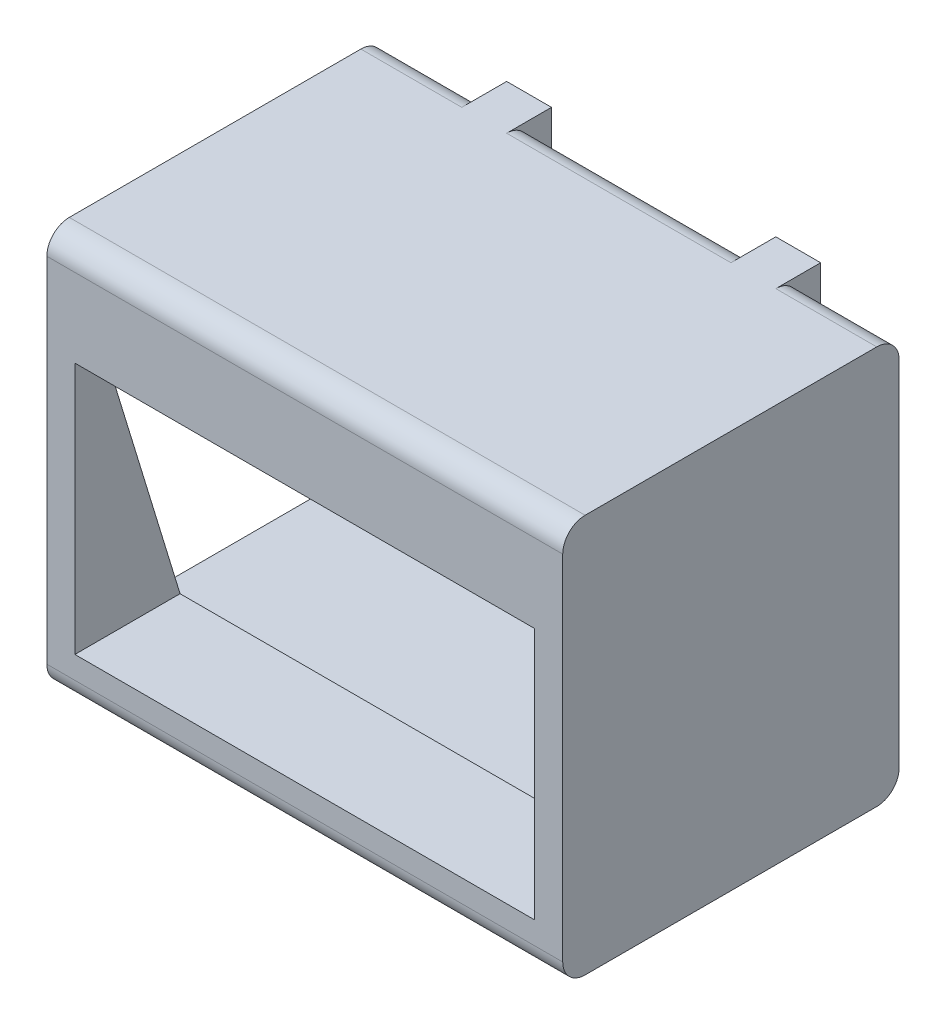
SolidWorks part; units mm, degrees
ref_plane "Front Plane" through (0, 0, 0) normal (0, 0, 1) x (1, 0, 0)
ref_plane "Top Plane" through (0, 0, 0) normal (0, 1, 0) x (1, 0, 0)
ref_plane "Right Plane" through (0, 0, 0) normal (1, 0, 0) x (0, 0, -1)
sketch "Sketch4" plane through (0, 0, 0) normal (1, 0, 0) x (0, 0, -1)
  line L1 (-30, 32.5) -> (30, 32.5)
  line L2 (-30, 32.5) -> (-30, -38.5)
  line L3 (-30, -38.5) -> (30, -38.5)
  line L4 (30, 32.5) -> (30, -38.5)
  dimension "D1" = 60
  dimension "D2" = 71
  dimension "D3" = 32.5
  dimension "D4" = 30
sketch "Sketch5" plane through (0, 0, 0) normal (1, 0, 0) x (0, 0, -1)
  line L0 (-25, 27.5) -> (-25, 14.5)
  line L1 (-25, 14.5) -> (-10.6307, -32.5)
  line L2 (-10.6307, -32.5) -> (25, -32.5)
  line L3 (25, -32.5) -> (25, 27.5)
  line L4 (25, 27.5) -> (-25, 27.5)
  line L5 (-30, 32.5) -> (-30, -38.5) construction
  line L6 (30, 32.5) -> (30, -38.5) construction
  line L7 (-30, 32.5) -> (30, 32.5) construction
  dimension "D1" = 107
  dimension "D2" = 13
  dimension "D3" = 60
  dimension "D4" = 50
  dimension "D5" = 25
  dimension "D6" = 27.5
  dimension "D7" = 5
  dimension "D8" = 5
  dimension "D9" = 5
extrude "Base" add sketch "Sketch4" along normal blind 46 and the other way blind 46
extrude "LIDAR" cut sketch "Sketch5" against normal up to surface (46 mm away) and the other way blind 41 up to face at (-46, -3, 0)
sketch "Sketch6" plane through (0, 0, 0) normal (0, 0, 1) x (1, 0, 0)
  line L0 (-46, 32.5) -> (-46, -38.5) construction
  line L1 (-41, 14.5) -> (41, 14.5)
  line L2 (-41, 14.5) -> (-41, -30.5)
  line L3 (-41, -30.5) -> (41, -30.5)
  line L4 (41, 14.5) -> (41, -30.5)
  line L5 (46, 32.5) -> (46, -38.5) construction
  line L6 (-46, 32.5) -> (46, 32.5) construction
  line L7 (-46, -38.5) -> (46, -38.5) construction
  dimension "D1" = 5
  dimension "D2" = 5
  dimension "D3" = 18
  dimension "D4" = 8
extrude "HoleFrontBack" cut sketch "Sketch6" against normal through all both and the other way through all
fillet "Fillet2" radius 4 4 edges at (0, 32.5, -30) (0, -38.5, -30) (0, -38.5, 30) (0, 32.5, 30)
sketch "Sketch9" plane through (0, 0, 0) normal (0, 1, 0) x (1, 0, 0)
  line L0 (-46, 26) -> (-46, -26) construction
  line L1 (46, 26) -> (-46, 26) construction
  circle A0 centre (-42.9, 22.29) radius 1
  dimension "D1" = 2
  dimension "D2" = 3.1
  dimension "D3" = 3.71
sketch "Sketch10" plane through (0, -38.5, 0) normal (0, -1, 0) x (1, 0, 0)
  line L0 (-23.335, 14) -> (23.335, 14) construction
  line L1 (0, 30) -> (0, -30) construction
  line L2 (-46, 30) -> (46, 30) construction
  line L3 (46, -30) -> (-46, -30) construction
  line L4 (0, 14) -> (0, -18) construction
  circle A0 centre (-23.335, 14) radius 2
  circle A1 centre (23.335, 14) radius 2
  circle A2 centre (-23.335, -18) radius 2
  circle A3 centre (23.335, -18) radius 2
  dimension "D2" = 4
  dimension "D1" = 23.335
  dimension "D3" = 16
  dimension "D4" = 32
extrude "Cut-Extrude1" cut sketch "Sketch10" against normal blind 4
sketch "Sketch11" plane through (0, 0, -30) normal (0, 0, -1) x (-1, 0, 0)
  line L1 (-28, 32.5) -> (-20, 32.5)
  line L2 (-28, 32.5) -> (-28, -38.5)
  line L3 (-28, -38.5) -> (-20, -38.5)
  line L4 (-20, 32.5) -> (-20, -38.5)
  line L6 (-24, 32.5) -> (-24, -38.5) construction
  line L7 (20, 32.5) -> (28, 32.5)
  line L8 (20, 32.5) -> (20, -38.5)
  line L9 (20, -38.5) -> (28, -38.5)
  line L10 (28, 32.5) -> (28, -38.5)
  line L11 (-46, 32.5) -> (46, 32.5) construction
  line L12 (46, -38.5) -> (-46, -38.5) construction
  line L13 (0, 0) -> (24, 0) construction
  line L14 (24, 32.5) -> (24, -38.5) construction
  line L15 (0, 0) -> (-24, 0) construction
  point P4 (-24, 0)
  point P9 (24, 0)
  dimension "D1" = 8
  dimension "D2" = 24
  dimension "D3" = 24
extrude "Boss-Extrude1" add sketch "Sketch11" along normal blind 4 and the other way up to vertex (4 mm away) other way up to point (46, 32.5, -26)
sketch "Sketch12" plane through (0, 0, -34) normal (0, 0, -1) x (-1, 0, 0)
  line L0 (-24, 32.5) -> (-24, -38.5) construction
  line L1 (24, 32.5) -> (24, -38.5) construction
  line L3 (-24, 16) -> (-24, -16) construction
  circle A0 centre (-24, 16) radius 2
  circle A1 centre (24, 16) radius 2
  circle A2 centre (-24, -16) radius 2
  circle A3 centre (24, -16) radius 2
  point P8 (-24, 0)
  dimension "D1" = 4
  dimension "D2" = 32
extrude "Cut-Extrude2" cut sketch "Sketch12" against normal blind 4 contours A0 | A2 | A3 | A1
